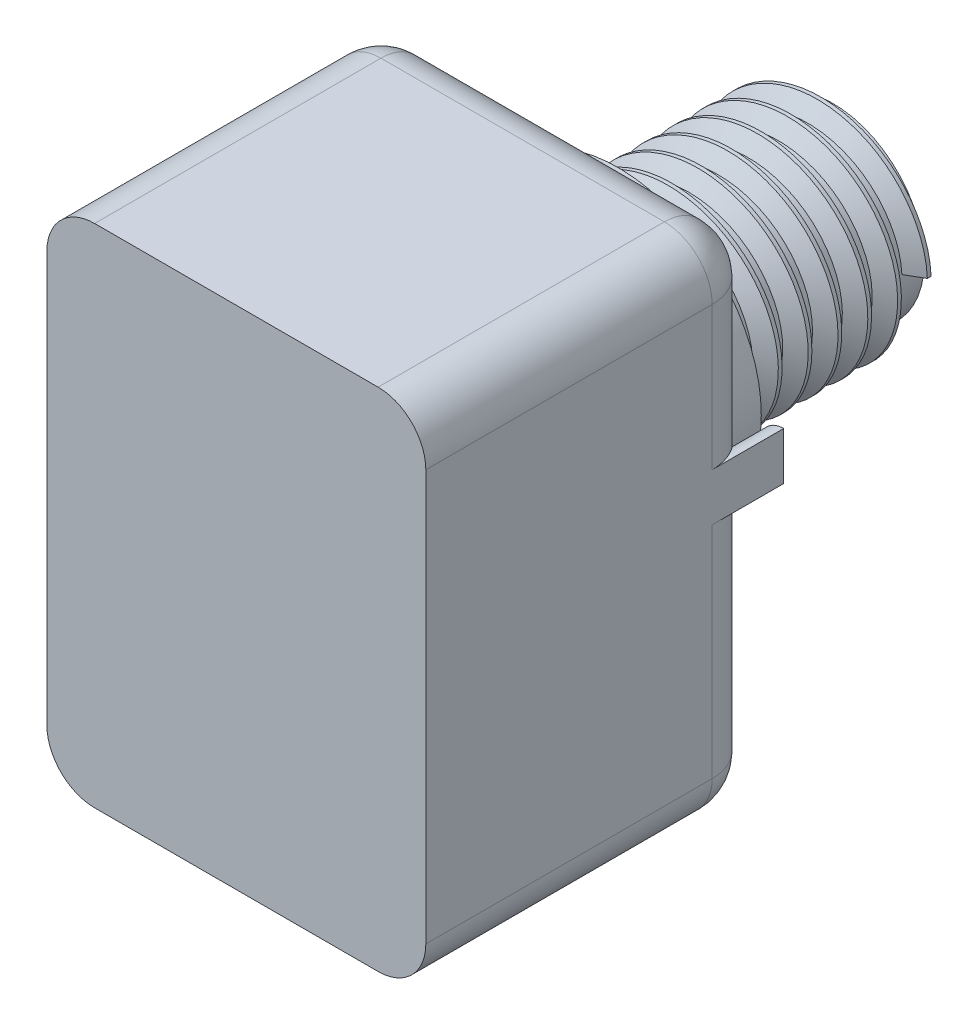
SolidWorks part; units mm, degrees
ref_plane "Płaszczyzna przednia" through (0, 0, 0) normal (0, 0, 1) x (1, 0, 0)
ref_plane "Płaszczyzna górna" through (0, 0, 0) normal (0, 1, 0) x (1, 0, 0)
ref_plane "Płaszczyzna prawa" through (0, 0, 0) normal (1, 0, 0) x (0, 0, -1)
sketch "Szkic1" plane through (0, 0, 0) normal (0, 0, 1) x (1, 0, 0)
  circle A0 centre (0, 0) radius 3
  dimension "D1" = 6
extrude "Dodanie-wyciągnięcie1" add sketch "Szkic1" along normal blind 13
sketch "Szkic2" plane through (0, 0, 13) normal (0, 0, 1) x (1, 0, 0)
  circle A0 centre (0, 0) radius 3.83
  dimension "D1" = 7.66
extrude "Dodanie-wyciągnięcie2" add sketch "Szkic2" along normal blind 9
thread "Gwint1" pitch 1.25 method extrude profile "Profil gwintu1" start angle 0, offset 0, length 10, pitch 1.25, diameter 7.66
ref_plane "Płaszczyzna4" through (3.83, 0, 13) normal (0, -1, 0) x (1, 0, 0)
sketch "Profil gwintu1" plane through (3.83, 0, 13) normal (0, -1, 0) x (1, 0, 0)
  line L0 (0, 0) -> (0, 1.25) construction
  line L1 (0, 0) -> (0.6766, 0.3906)
  line L2 (0.6766, 0.3906) -> (0.6766, 0.5469)
  line L3 (0.6766, 0.5469) -> (0, 0.9375)
  line L4 (0.6766, 0.4687) -> (0, 0.4687) construction
  line L11 (0, 0) -> (0, 0.9375)
  point P2 (0, 0)
  dimension "Pitch" = 1.25
  dimension "Profile_Angle" = 60
  dimension "Profile_Land" = 0.1562
  dimension "Profile_Height" = 0.6766
sketch "Szkic6" plane through (0, 0, 22) normal (0, 0, 1) x (1, 0, 0)
  circle A0 centre (0, 0) radius 6
  dimension "D1" = 12
extrude "Dodanie-wyciągnięcie3" add sketch "Szkic6" along normal blind 2
sketch "Szkic8" plane through (0, 0, 24) normal (0, 0, 1) x (1, 0, 0)
  line L0 (0, 9) -> (-7.94, 9) construction
  line L1 (-7.94, 9) -> (7.94, 9)
  line L2 (-7.94, 9) -> (-7.94, -12.21)
  line L3 (-7.94, -12.21) -> (7.94, -12.21)
  line L4 (7.94, 9) -> (7.94, -12.21)
  line L5 (0, -12.21) -> (0, 9) construction
  dimension "D1" = 15.88
  dimension "D2" = 21.21
  dimension "D3" = 9
extrude "Dodanie-wyciągnięcie4" add sketch "Szkic8" along normal blind 14
fillet "Zaokrąglenie1" radius 2 8 edges at (7.94, -1.605, 24) (0, -12.21, 24) (-7.94, -1.605, 24) (0, 9, 24) (-7.94, -12.21, 31) (7.94, -12.21, 31) (-7.94, 9, 31) (7.94, 9, 31)
sketch "Szkic9" plane through (0, 0, 0) normal (0, 0, -1) x (-1, 0, 0)
  line L0 (-1.5964, -2.54) -> (1.5964, -2.54)
  line L1 (-1.5964, -2.54) -> (-7.8481, -6.1903)
  line L2 (-7.8481, -6.1903) -> (8.0345, -6.6875)
  line L3 (8.0345, -6.6875) -> (1.5964, -2.54)
  circle A0 centre (0, 0) radius 3 construction
  circle A1 centre (0, 0) radius 3 construction
  point P4 (0, 3)
  dimension "D1" = 5.54
extrude "Wytnij-wyciągnięcie1" cut sketch "Szkic9" against normal blind 9
sketch "Szkic10" plane through (0, 0, 0) normal (0, 0, 1) x (1, 0, 0)
  line L0 (0, 0) -> (7.94, 0) construction
  line L1 (7.94, -0.8464) -> (7.94, 0.8464) construction
  line L2 (7.94, 0) -> (7.94, 1)
  line L3 (7.94, 0) -> (7.94, -1)
  arc A0 (7.94, 1) -> (7.94, -1) centre (7.94, 0) ccw
  dimension "D1" = 1
  dimension "D2" = 1
  dimension "D3" = 7.94
extrude "Dodanie-wyciągnięcie6" add sketch "Szkic10" along normal up to next from surface starting at face at (0, 5.2116, 24)
extrude "Dodanie-wyciągnięcie7" add sketch "Szkic10<2>" against normal blind 1 from surface starting at face at (0, -6.8166, 24)
sketch "Szkic10<2>" plane through (0, 0, 0) normal (0, 0, 1) x (1, 0, 0) same geometry as "Szkic10"
sketch "Szkic11" plane through (0, 0, 13) normal (0, 0, -1) x (-1, 0, 0)
  circle A0 centre (0, 0) radius 9.0974
extrude "Wytnij-wyciągnięcie2" cut sketch "Szkic11" along normal through all
